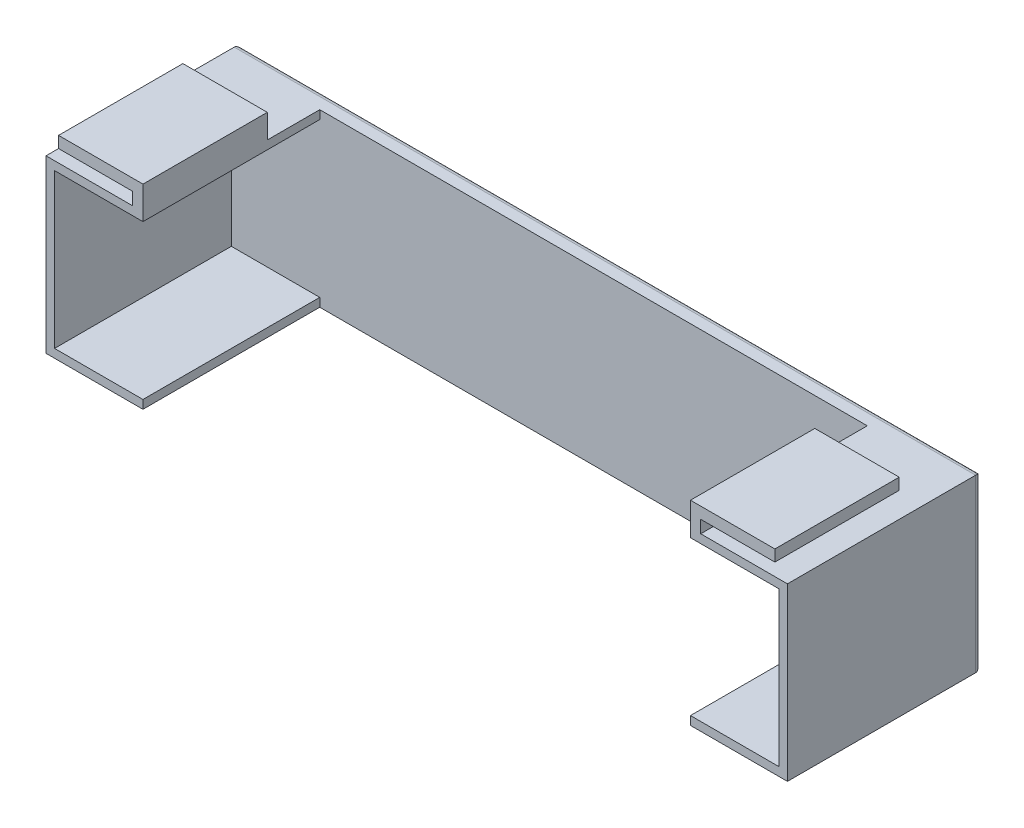
SolidWorks part; units mm, degrees
ref_plane "Plan de face" through (0, 0, 0) normal (0, 0, 1) x (1, 0, 0)
ref_plane "Plan de dessus" through (0, 0, 0) normal (0, 1, 0) x (1, 0, 0)
ref_plane "Plan de droite" through (0, 0, 0) normal (1, 0, 0) x (0, 0, -1)
sketch "Esquisse1" plane through (0, 0, 0) normal (0, 0, 1) x (1, 0, 0)
  line L1 (0, 0) -> (130, 0)
  line L2 (0, 0) -> (0, 30)
  line L3 (0, 30) -> (130, 30)
  line L4 (130, 0) -> (130, 30)
  dimension "D1" = 30
  dimension "D2" = 130
extrude "Boss.-Extru.1" add sketch "Esquisse1" along normal blind 1
sketch "Esquisse2" plane through (0, 0, 1) normal (0, 0, 1) x (1, 0, 0)
  line L0 (128.5, 28.5) -> (113, 28.5)
  line L1 (1.5, 28.5) -> (1.5, 1.5)
  line L2 (1.5, 1.5) -> (17, 1.5)
  line L3 (128.5, 1.5) -> (128.5, 28.5)
  line L4 (0, 30) -> (0, 0)
  line L5 (0, 0) -> (130, 0)
  line L6 (130, 0) -> (130, 30)
  line L7 (130, 30) -> (0, 30)
  line L8 (0, 30) -> (0, 0)
  line L9 (0, 0) -> (17, 0)
  line L10 (130, 0) -> (130, 30)
  line L11 (130, 30) -> (113, 30)
  line L13 (17, 30) -> (17, 28.5)
  line L14 (113, 30) -> (113, 28.5)
  line L15 (17, 1.5) -> (17, 0)
  line L18 (17, 28.5) -> (1.5, 28.5)
  line L20 (17, 30) -> (0, 30)
  line L22 (113, 0) -> (130, 0)
  line L24 (113, 1.5) -> (128.5, 1.5)
  line L26 (113, 1.5) -> (113, 0)
  dimension "D2" = 1.5
  dimension "D3" = 1.5
  dimension "D4" = 1.5
  dimension "D5" = 1.5
  dimension "D6" = 15.5
  dimension "D1" = 0
extrude "Boss.-Extru.2" add sketch "Esquisse2" along normal blind 31
sketch "Esquisse3" plane through (0, 0, 0) normal (0, 0, -1) x (-1, 0, 0)
  line L1 (-128, 28) -> (-2, 28)
  line L2 (-128, 28) -> (-128, 2)
  line L3 (-128, 2) -> (-2, 2)
  line L4 (0, 0) -> (0, 30)
  line L5 (0, 30) -> (-130, 30)
  line L6 (-130, 30) -> (-130, 0)
  line L7 (-130, 0) -> (0, 0)
  line L8 (0, 0) -> (0, 30)
  line L9 (0, 30) -> (-130, 30)
  line L10 (-130, 30) -> (-130, 0)
  line L11 (-130, 0) -> (0, 0)
  line L12 (-2, 28) -> (-2, 2)
  dimension "D2" = 2
  dimension "D3" = 2
  dimension "D4" = 2
  dimension "D5" = 2
  dimension "D1" = 0
sketch "Esquisse5" plane through (0, 30, 0) normal (0, 1, 0) x (1, 0, 0)
  line L0 (65, -1) -> (65, -32) construction
  line L1 (17, -32) -> (15.2, -32)
  line L2 (17, -32) -> (17, -10.2)
  line L3 (17, -10.2) -> (15.2, -10.2)
  line L4 (15.2, -32) -> (15.2, -10.2)
  line L5 (113, -1) -> (17, -1) construction
  line L7 (114.8, -32) -> (114.8, -10.2)
  line L8 (113, -10.2) -> (114.8, -10.2)
  line L9 (113, -32) -> (113, -10.2)
  line L10 (113, -32) -> (114.8, -32)
  dimension "D1" = 1.8
  dimension "D2" = 21.8
extrude "Boss.-Extru.4" add sketch "Esquisse5" along normal blind 2.2
sketch "Esquisse6" plane through (0, 32.2, 0) normal (0, 1, 0) x (1, 0, 0)
  line L0 (65, -1) -> (65, -32.2011) construction
  line L1 (113, -1) -> (17, -1) construction
  line L2 (0, -32) -> (0, 0) construction
  line L3 (17, -32) -> (2.2, -32)
  line L4 (17, -32) -> (17, -10.2)
  line L5 (17, -10.2) -> (2.2, -10.2)
  line L6 (2.2, -32) -> (2.2, -10.2)
  line L7 (17, -10.2) -> (15.2, -10.2) construction
  line L8 (127.8, -32) -> (127.8, -10.2)
  line L9 (113, -10.2) -> (127.8, -10.2)
  line L10 (113, -32) -> (113, -10.2)
  line L11 (113, -32) -> (127.8, -32)
  dimension "D1" = 2.2
extrude "Boss.-Extru.5" add sketch "Esquisse6" along normal blind 2
extrude "Boss.-Extru.3" add sketch "Esquisse3" along normal blind 2
fillet "Congé1" radius 1 12 edges at (65, 28, 0) (2, 15, 0) (65, 2, 0) (128, 15, 0) (2, 15, -2) (65, 28, -2) (128, 15, -2) (65, 2, -2) (130, 15, -2) (65, 30, -2) (0, 15, -2) (65, 0, -2)
